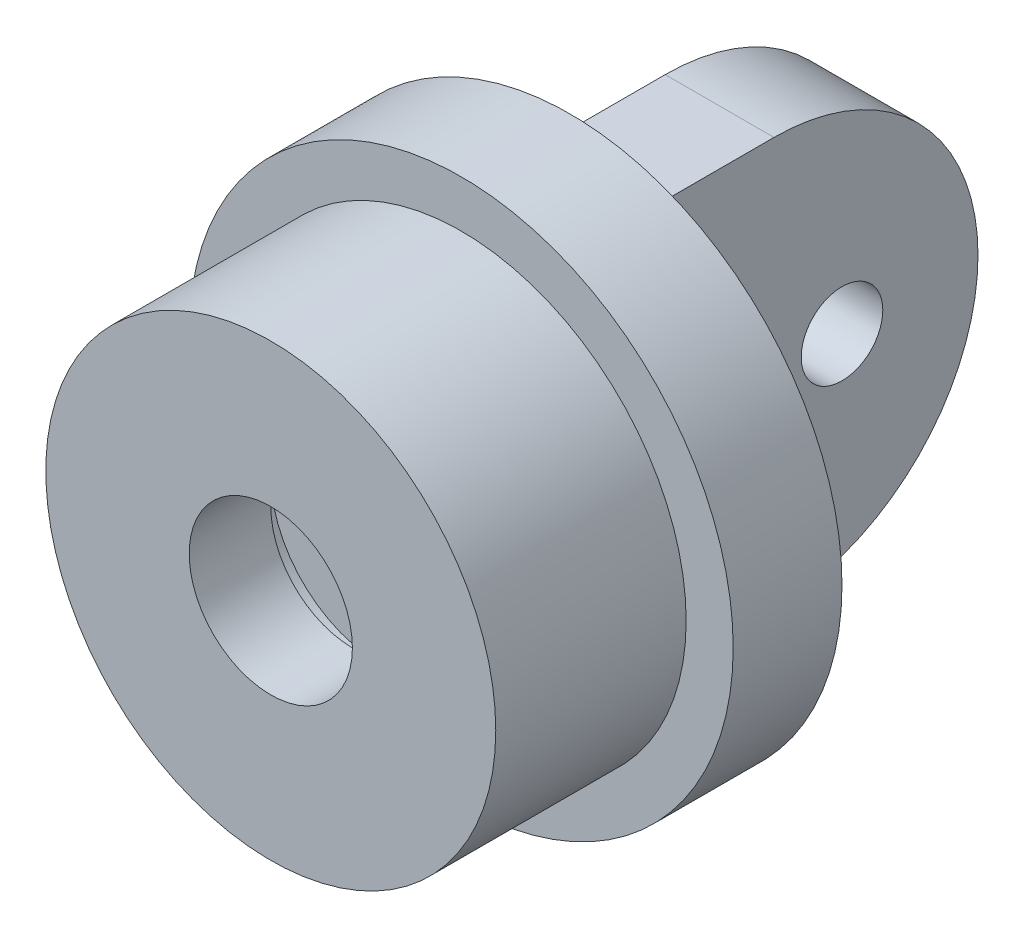
SolidWorks part; units mm, degrees
ref_plane "Front" through (0, 0, 0) normal (0, 0, 1) x (1, 0, 0)
ref_plane "Top" through (0, 0, 0) normal (0, 1, 0) x (1, 0, 0)
ref_plane "Right" through (0, 0, 0) normal (1, 0, 0) x (0, 0, -1)
sketch "Sketch1" plane through (0, 0, 0) normal (0, 0, 1) x (1, 0, 0)
  circle A0 centre (0, 0) radius 50
  dimension "D1" = 100
extrude "Boss-Extrude1" add sketch "Sketch1" along normal blind 20
sketch "Sketch2" plane through (0, 0, 0) normal (0, 0, -1) x (-1, 0, 0)
  line L1 (-10, -37.5) -> (10, -37.5)
  line L2 (-10, -37.5) -> (-10, 37.5)
  line L3 (-10, 37.5) -> (10, 37.5)
  line L4 (10, -37.5) -> (10, 37.5)
  line L5 (-10, -37.5) -> (10, 37.5) construction
  line L6 (-10, 37.5) -> (10, -37.5) construction
  circle A1 centre (0, 0) radius 50
  circle A2 centre (0, 0) radius 50
  dimension "D2" = 75
  dimension "D3" = 20
  dimension "D1" = 0
extrude "Boss-Extrude2" add sketch "Sketch2" along normal blind 65 contours L4 L3 L2 L1
sketch "Sketch3" plane through (10, 0, 0) normal (1, 0, 0) x (0, 0, -1)
  circle A0 centre (39.9968, 0) radius 7.5
  dimension "D1" = 15
extrude "Cut-Extrude1" cut sketch "Sketch3" against normal blind 65 contours A0
fillet "Fillet1" radius 37.5 2 edges at (0, -37.5, -65) (0, 37.5, -65)
sketch "Sketch4" plane through (0, 0, 20) normal (0, 0, 1) x (1, 0, 0)
  circle A0 centre (0, 0) radius 41.3556
extrude "Boss-Extrude3" add sketch "Sketch4" along normal blind 35
sketch "Sketch8" plane through (0, 0, 55) normal (0, 0, 1) x (1, 0, 0)
  circle A0 centre (0, 0) radius 15
extrude "Cut-Extrude2" cut sketch "Sketch8" against normal blind 20
sketch "Sketch10" plane through (0, 0, 0) normal (1, 0, 0) x (0, 0, -1)
  line L4 (-55, 0) -> (-14.2323, 0) construction
  line L5 (-55, 41.3556) -> (-55, -41.3556) construction
  line L7 (-35, 20) -> (-40, 20)
  line L8 (-35, 20) -> (-35, 11.5537)
  line L9 (-35, 11.5537) -> (-40, 11.5537)
  line L10 (-40, 20) -> (-40, 11.5537)
  dimension "D2" = 5
revolve "Cut-Revolve1" cut sketch "Sketch10" angle 360 about L4
